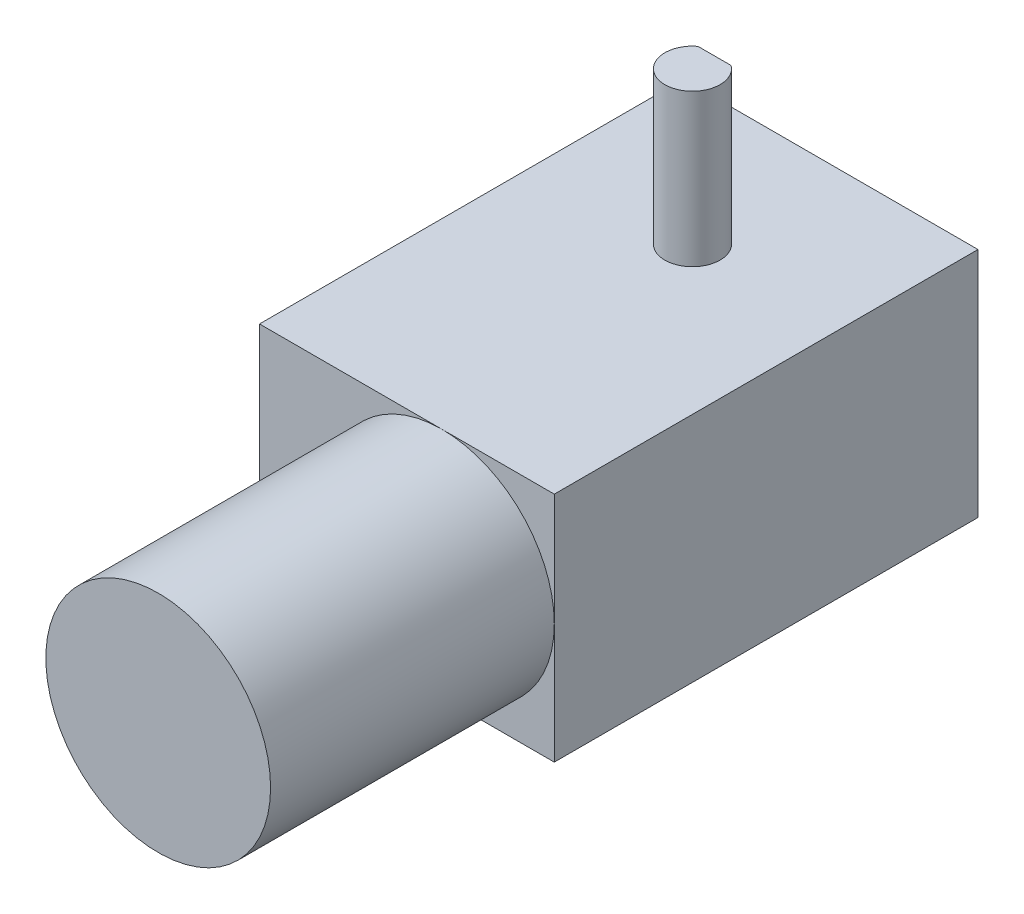
SolidWorks part; units mm, degrees
ref_plane "Front Plane" through (0, 0, 0) normal (0, 0, 1) x (1, 0, 0)
ref_plane "Top Plane" through (0, 0, 0) normal (0, 1, 0) x (1, 0, 0)
ref_plane "Right Plane" through (0, 0, 0) normal (1, 0, 0) x (0, 0, -1)
sketch "Sketch1" plane through (0, 0, 0) normal (0, 1, 0) x (1, 0, 0)
  line L0 (-1.8, 2.4) -> (1.8, 2.4)
  line L1 (-16, -31) -> (16, -31)
  line L2 (-16, -31) -> (-16, 15)
  line L3 (-16, 15) -> (16, 15)
  line L4 (16, -31) -> (16, 15)
  arc A0 (-1.8, 2.4) -> (1.8, 2.4) centre (0, 0) ccw
  point P5 (0, -31)
  dimension "D2" = 6
  dimension "D5" = 15
  dimension "D1" = 2.4
  dimension "D3" = 32
  dimension "D4" = 46
extrude "Boss-Extrude1" add sketch "Sketch1" along normal blind 25.2 contours L1 L4 L3 L2 A0 L0 | L0 A0 region at (0, 0, 0.1451) region at (0, 0, 8.1457)
extrude "Boss-Extrude2" add sketch "Sketch1<3>" along normal blind 16.5 from surface contours A0 L0 starting at face at (0, 25.2, 8)
sketch "Sketch1<3>" plane through (0, 0, 0) normal (0, 1, 0) x (1, 0, 0) same geometry as "Sketch1"
sketch "Sketch2" plane through (0, 0, 31) normal (0, 0, 1) x (1, 0, 0)
  line L0 (16, 25.2) -> (16, 0) construction
  line L1 (-16, 25.2) -> (16, 25.2) construction
  circle A0 centre (3.8, 13) radius 12.2
  dimension "D1" = 24.4
extrude "Boss-Extrude3" add sketch "Sketch2" along normal blind 30.8
